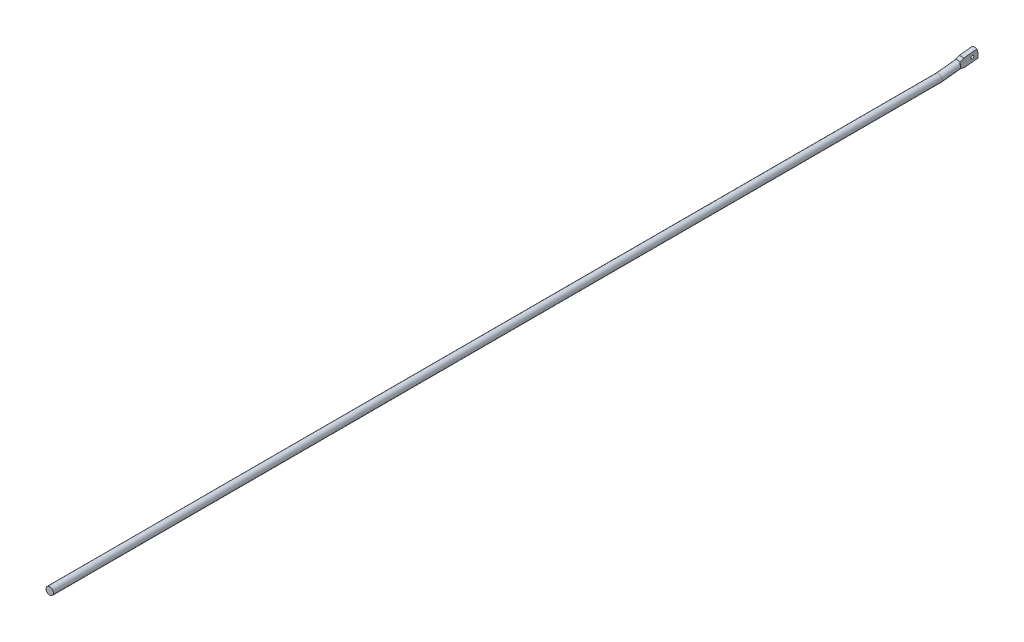
SolidWorks part; units mm, degrees
material "1023 Carbon Steel Sheet (SS)"
ref_plane "Front Plane" through (0, 0, 0) normal (0, 0, 1) x (1, 0, 0)
ref_plane "Top Plane" through (0, 0, 0) normal (0, 1, 0) x (1, 0, 0)
ref_plane "Right Plane" through (0, 0, 0) normal (1, 0, 0) x (0, 0, -1)
sketch "Sketch4" plane through (0, 0, 0) normal (1, 0, 0) x (0, 0, -1)
  line L0 (0, 0) -> (1000, 0) construction
  line L1 (0, 0) -> (960, 0)
  line L2 (960, 0) -> (1000, 4.2042)
  dimension "D1" = 1000
  dimension "D2" = 960
  dimension "D3" = 6
sketch "Sketch5" plane through (0, 0, 0) normal (0, 0, 1) x (1, 0, 0)
  circle A0 centre (0, 0) radius 4
  dimension "D1" = 8
sweep "Sweep1" add profiles "Sketch5" path "Sketch4"
sketch "Sketch6" plane through (0, 104.0018, -989.5108) normal (0, 0.1045, -0.9945) x (-1, 0, 0)
  line L2 (-2.5, -100.3473) -> (-2.5, -94.9185)
  line L3 (-2.5, -94.9185) -> (2.5, -94.9185)
  line L4 (2.5, -94.9185) -> (2.5, -104.7457)
  line L5 (2.5, -104.7457) -> (-2.5, -104.7457)
  line L6 (-2.5, -104.7457) -> (-2.5, -100.3473)
  point P10 (0, -100.3473)
extrude "Cut-Extrude2" cut sketch "Sketch6" against normal blind 19 flip side to cut
sketch "Sketch7" plane through (0, 104.0018, -989.5108) normal (0, 0.1045, -0.9945) x (-1, 0, 0)
  line L2 (-2.5, -97.2248) -> (-2.5, -103.4698)
  line L3 (2.5, -103.4698) -> (2.5, -97.2248)
  line L4 (-2.5, -97.2248) -> (-2.5, -103.4698)
  line L5 (2.5, -103.4698) -> (2.5, -97.2248)
  line L6 (-2.5, -103.4698) -> (-2.5, -104.9639)
  line L8 (2.5, -103.4698) -> (2.5, -104.9639)
  line L9 (-2.5, -97.2248) -> (-2.5, -95.7308)
  line L11 (2.5, -97.2248) -> (2.5, -95.7308)
  line L13 (-3.75, -96.6731) -> (-3.75, -104.0216) construction
  line L14 (3.75, -104.0216) -> (3.75, -96.6731) construction
  arc A0 (-2.5, -104.9639) -> (2.5, -104.9639) centre (0, -100.3473) ccw
  arc A1 (2.5, -95.7308) -> (-2.5, -95.7308) centre (0, -100.3473) ccw
  arc A2 (-2.5, -103.4698) -> (2.5, -103.4698) centre (0, -100.3473) ccw
  arc A3 (2.5, -97.2248) -> (-2.5, -97.2248) centre (0, -100.3473) ccw
  arc A6 (2.5, -97.2248) -> (-2.5, -97.2248) centre (0, -100.3473) ccw construction
  arc A7 (-2.5, -103.4698) -> (2.5, -103.4698) centre (0, -100.3473) ccw construction
  arc A8 (3.75, -96.6731) -> (-3.75, -96.6731) centre (0, -100.3473) ccw construction
  arc A9 (-3.75, -104.0216) -> (3.75, -104.0216) centre (0, -100.3473) ccw construction
  dimension "D1" = 0
  dimension "D2" = 1.25
extrude "Boss-Extrude2" add sketch "Sketch7" against normal blind 19
sketch "Sketch8" plane through (-2.5, 0, 0) normal (-1, 0, 0) x (0, 0, 1)
  line L5 (-980.7777, 5.3235) -> (-981.4305, -0.8873) construction
  line L8 (-999.8131, -1.0944) -> (-1000.1398, -2.7828)
  line L9 (-1000.1398, -2.7828) -> (-1007.1221, 2.7322)
  line L10 (-1007.1221, 2.7322) -> (-999.9764, 14.3187)
  line L11 (-999.9764, 14.3187) -> (-998.7155, 9.3481)
  arc A0 (-998.7155, 9.3481) -> (-999.8131, -1.0944) centre (-981.1041, 2.2181) ccw
extrude "Cut-Extrude6" cut sketch "Sketch8" against normal blind 10
ref_plane "Plane1" through (0, -105.0189, -11.0379) normal (0, -0.9945, -0.1045) x (-1, 0, 0)
sketch "Sketch9" plane through (0, -105.0189, -11.0379) normal (0, -0.9945, -0.1045) x (-1, 0, 0)
  line L0 (2.5, 975.9614) -> (2.5, 974.4614) construction
  line L1 (2.5, 975.9614) -> (4, 974.4614)
  line L2 (4, 954.741) -> (4, 975.9614) construction
  line L3 (4, 974.4614) -> (-4, 974.4614) construction
  line L4 (-4, 975.9614) -> (-4, 954.741) construction
  line L5 (4, 974.4614) -> (4.986, 974.4614)
  line L6 (4.986, 974.4614) -> (4.986, 997.5745)
  line L7 (4.986, 997.5745) -> (-6.2295, 997.5745)
  line L8 (-6.2295, 997.5745) -> (-6.2295, 974.4614)
  line L9 (-6.2295, 974.4614) -> (-4, 974.4614)
  line L10 (-4, 974.4614) -> (-2.5, 975.9614)
  line L11 (-2.5, 975.9614) -> (-2.5, 995.9407)
  line L12 (-2.5, 995.9407) -> (2.5, 995.9407)
  line L13 (2.5, 995.9407) -> (2.5, 975.9614)
  dimension "D1" = 1.5
extrude "Cut-Extrude4" cut sketch "Sketch9" against normal blind 19
chamfer "Chamfer4" distance 1.25 distance2 4 2 edges at (0, 7.4394, -980.5553) (0, -3.0031, -981.6529) first distance on face at (0, 6.4421, -980.6601) first distance on face at (0, -2.0059, -981.548)
sketch "Sketch10" plane through (2.5, 0, 0) normal (1, 0, 0) x (0, 0, -1)
  circle A1 centre (993.9781, 3.5712) radius 1.625
  dimension "D2" = 3.25
extrude "Cut-Extrude5" cut sketch "Sketch10" against normal blind 19
